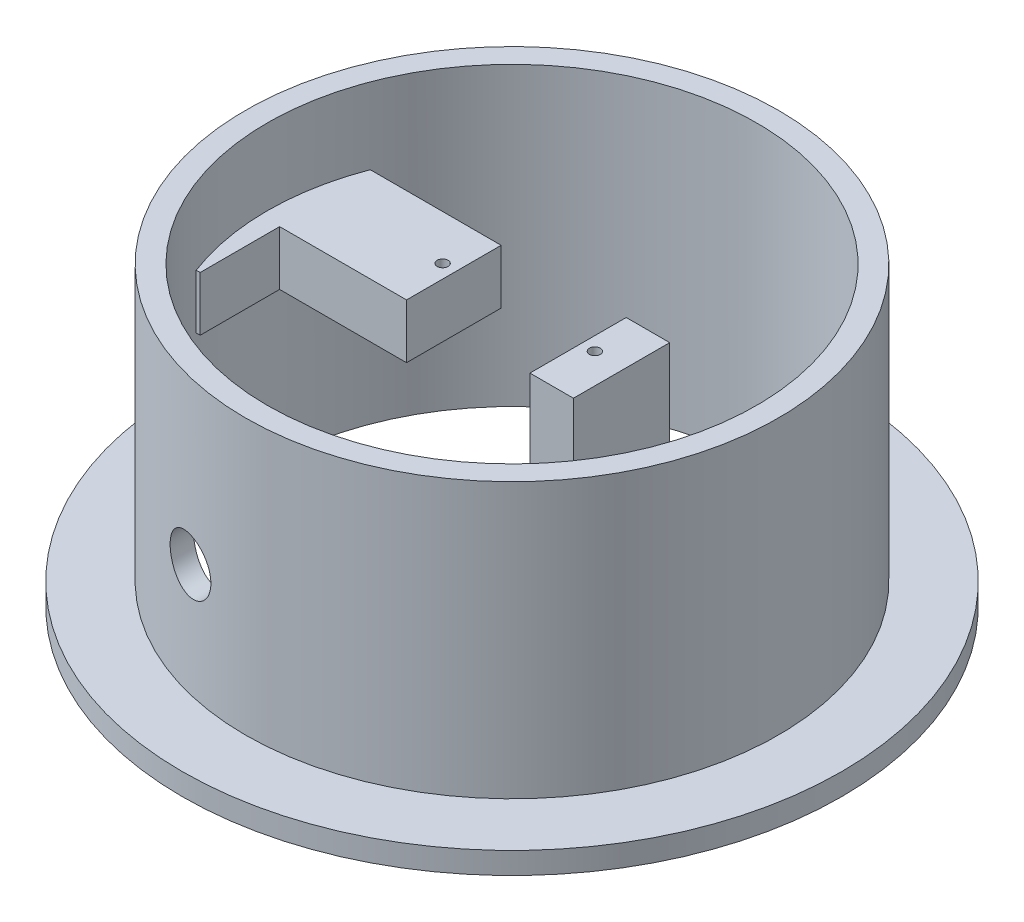
SolidWorks part; units mm, degrees
ref_plane "Front Plane" through (0, 0, 0) normal (0, 0, 1) x (1, 0, 0)
ref_plane "Top Plane" through (0, 0, 0) normal (0, 1, 0) x (1, 0, 0)
ref_plane "Right Plane" through (0, 0, 0) normal (1, 0, 0) x (0, 0, -1)
sketch "Sketch1" plane through (0, 0, 0) normal (0, 1, 0) x (1, 0, 0)
  circle A0 centre (0, 0) radius 60.625
  circle A1 centre (0, 0) radius 45
  dimension "D1" = 121.25
  dimension "D2" = 90
extrude "Boss-Extrude1" add sketch "Sketch1" along normal blind 4
sketch "Sketch2" plane through (0, 4, 0) normal (0, 1, 0) x (1, 0, 0)
  circle A0 centre (0, 0) radius 45 construction
  circle A1 centre (0, 0) radius 45
  circle A2 centre (0, 0) radius 49
  dimension "D1" = 4
extrude "Boss-Extrude2" add sketch "Sketch2" along normal blind 50.5
ref_plane "Plane1" through (0, 34.5, 0) normal (0, 1, 0) x (1, 0, 0)
sketch "Sketch4" plane through (0, 0, 0) normal (0, 0, 1) x (1, 0, 0)
  line L0 (-60.625, 0) -> (60.625, 0) construction
  line L1 (5, 40.5) -> (13, 40.5)
  line L2 (5, 40.5) -> (5, 0)
  line L3 (5, 0) -> (13, 0)
  line L4 (13, 40.5) -> (13, 0)
  line L5 (49, 54.5) -> (-49, 54.5) construction
  line L6 (-45, 54.5) -> (-45, 4)
  line L7 (-18, 40.5) -> (-45, 40.5)
  line L8 (-18, 40.5) -> (-18, 30.5)
  line L9 (-18, 30.5) -> (-45, 30.5)
  line L10 (-45, 40.5) -> (-45, 30.5)
  line L11 (60.625, 4) -> (-60.625, 4) construction
  line L12 (-18, 30.5) -> (-45, 3.5)
  dimension "D1" = 5
  dimension "D2" = 8
  dimension "D3" = 14
  dimension "D4" = 23
  dimension "D5" = 27
  dimension "D6" = 10
  dimension "D7" = 45
  dimension "D8" = 14
extrude "Boss-Extrude4" add sketch "Sketch4" along normal mid plane 32 contours L9 L8 L7 L6 | L12 L9 L6 | L1 L4 L3 L2 region at (-31.5, 35.5, 0)
sketch "Sketch5" plane through (0, 0, 0.8324) normal (0, -1, 0) x (1, 0, 0)
  line L0 (0.9227, 14.5796) -> (36.1058, 30.1379)
  line L1 (0.9227, -16.0291) -> (36.6512, -32.9046)
  line L2 (0.9227, 14.5796) -> (0.9227, -16.0291)
  arc A1 (36.6512, -32.9046) -> (36.1058, 30.1379) centre (-2.8733, -1.7229) ccw
extrude "Boss-Extrude5" add sketch "Sketch5" against normal up to surface (4 mm away) contours L0 A1 L1 L2 up to face at (0, 4, 60.625)
sketch "Sketch6" plane through (0, 0, 0) normal (0, 0, 1) x (1, 0, 0)
  circle A0 centre (-11.8474, 24.4856) radius 5
extrude "Cut-Extrude2" cut sketch "Sketch6" along normal blind 52 contours A0
sketch "Sketch7" plane through (0, 40.5, 0) normal (0, 1, 0) x (1, 0, 0)
  line L0 (-18, -16) -> (-18, 16) construction
  line L1 (5, -16) -> (5, 16) construction
  circle A0 centre (-20.5, 7.7399) radius 1
  circle A1 centre (7.5, 7.7399) radius 1
  dimension "D1" = 2.5
  dimension "D2" = 2.5
extrude "Cut-Extrude3" cut sketch "Sketch7" against normal blind 4.5
sketch "Sketch8" plane through (0, 40.5, 0.701) normal (0, 1, 0) x (1, 0, 0)
  line L1 (5, -1) -> (13, -1)
  line L2 (5, -1) -> (5, -16)
  line L3 (5, -16) -> (13, -16)
  line L4 (13, -1) -> (13, -16)
  dimension "D1" = 8
  dimension "D2" = 15
sketch "Sketch9" plane through (0, 40.5, 0.701) normal (0, 1, 0) x (1, 0, 0)
  line L1 (-41.34, -0.6916) -> (-16.34, -0.6916)
  line L2 (-41.34, -0.6916) -> (-41.34, -16.5689)
  line L3 (-41.34, -16.5689) -> (-16.34, -16.5689)
  line L4 (-16.34, -0.6916) -> (-16.34, -16.5689)
  dimension "D1" = 25
  dimension "D2" = 15.8773
extrude "Cut-Extrude5" cut sketch "Sketch9" against normal blind 35
sketch "Sketch11" plane through (0, 4, 0) normal (0, 1, 0) x (1, 0, 0)
  line L0 (16.2655, 12.7324) -> (16.2655, -6.5497)
  line L1 (16.2655, -6.5497) -> (5.715, -6.5497)
  line L2 (5.715, -6.5497) -> (5.715, -11.643)
  line L3 (5.715, -11.643) -> (30.818, -22.5574)
  line L4 (16.2655, 12.7324) -> (32.152, 20.615)
  arc A0 (32.152, 20.615) -> (30.818, -22.5574) centre (5.8984, -0.1806) cw
extrude "Cut-Extrude6" cut sketch "Sketch11" against normal through all
extrude "Cut-Extrude7" cut sketch "Sketch8" against normal blind 36.5
